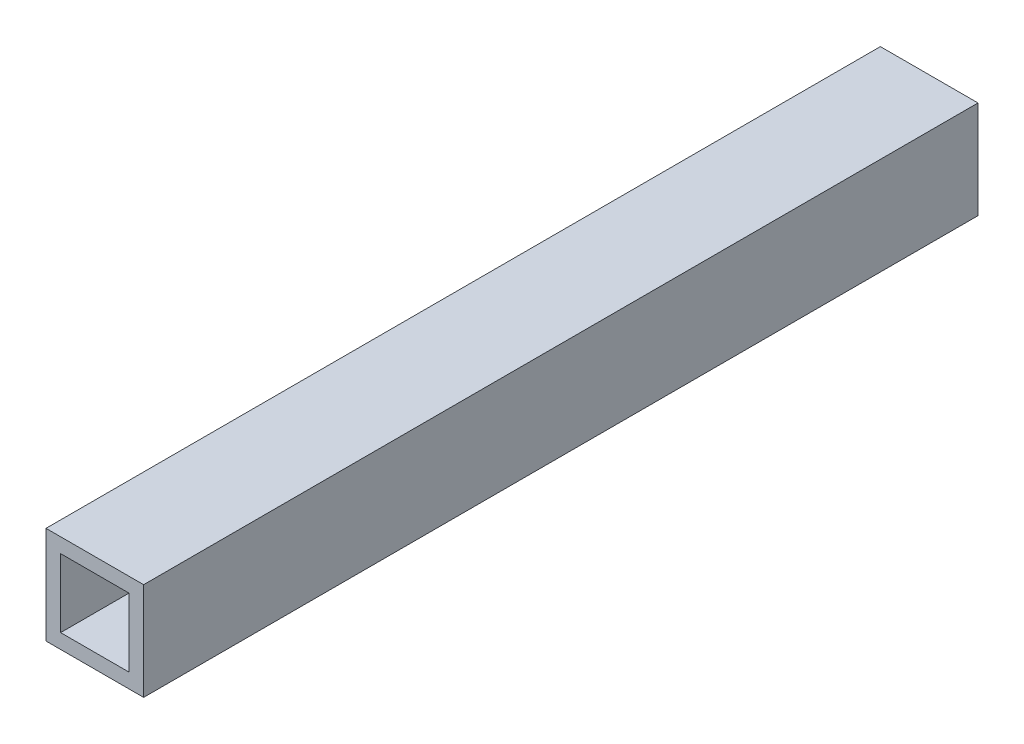
SolidWorks part; units mm, degrees
ref_plane "Plan de face" through (0, 0, 0) normal (0, 0, 1) x (1, 0, 0)
ref_plane "Plan de dessus" through (0, 0, 0) normal (0, 1, 0) x (1, 0, 0)
ref_plane "Plan de droite" through (0, 0, 0) normal (1, 0, 0) x (0, 0, -1)
sketch "Esquisse1" plane through (0, 0, 0) normal (0, 0, 1) x (1, 0, 0)
  line L1 (0, 0) -> (11.7, 0)
  line L2 (0, 0) -> (0, 11.7)
  line L3 (0, 11.7) -> (11.7, 11.7)
  line L4 (11.7, 0) -> (11.7, 11.7)
  line L5 (1.75, 1.75) -> (9.95, 1.75)
  line L6 (1.75, 1.75) -> (1.75, 9.95)
  line L7 (1.75, 9.95) -> (9.95, 9.95)
  line L8 (9.95, 1.75) -> (9.95, 9.95)
  dimension "D1" = 11.7
  dimension "D2" = 11.7
  dimension "D3" = 8.2
  dimension "D4" = 8.2
  dimension "D5" = 1.75
  dimension "D6" = 1.75
  dimension "D7" = 1.75
extrude "Boss.-Extru.1" add sketch "Esquisse1" along normal blind 100
